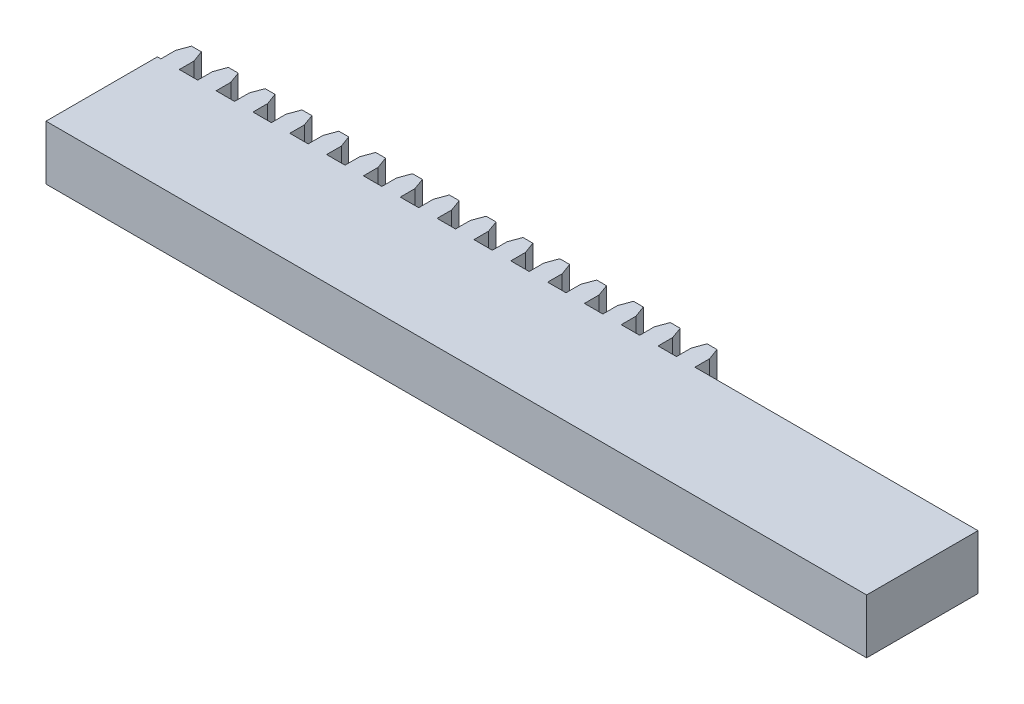
SolidWorks part; units mm, degrees
ref_plane "Front Plane" through (0, 0, 0) normal (0, 0, 1) x (1, 0, 0)
ref_plane "Top Plane" through (0, 0, 0) normal (0, 1, 0) x (1, 0, 0)
ref_plane "Right Plane" through (0, 0, 0) normal (1, 0, 0) x (0, 0, -1)
sketch "Sketch2" plane through (0, 0, 0) normal (0, 1, 0) x (1, 0, 0)
  line L0 (-1000, 0) -> (49000, 0) construction
  line L3 (0, -1000) -> (0, 49000) construction
  line L6 (-0.8429, 4.5) -> (0.8429, 4.5)
  line L7 (1.5708, 2.5) -> (1.5708, 0)
  line L8 (-1.5712, 2.5001) -> (-1.5712, 0)
  line L55 (0.8429, 4.5) -> (1.5708, 2.5)
  line L58 (-0.8429, 4.5) -> (-1.5712, 2.5001)
  line L509 (-65, 0) -> (65, 0)
  line L510 (-65, 0) -> (-65, -19)
  line L511 (-65, -19) -> (65, -19)
  line L512 (65, 0) -> (65, -19)
  point P1 (0, -19)
  point P8 (0, 4.5)
  dimension "D3" = 2
  dimension "D4" = 20
  dimension "D7" = 130
  dimension "D9" = 19
  dimension "D1" = 3.142
  dimension "D2" = 2.5
  dimension "D5" = 4.5
extrude "Boss-Extrude1" add sketch "Sketch2" along normal blind 9.3 contours L512 L509 L510 L511 region at (0, 0, 9.5)
extrude "Boss-Extrude2" add sketch "Sketch2<5>" along normal up to surface (9.3 mm away) contours L8 L509 L7 L55 L6 L58 region at (-0.0002, 0, -2.0682) up to face at (0, 9.3, 9.5)
sketch "Sketch2<5>" plane through (0, 0, 0) normal (0, 1, 0) x (1, 0, 0) same geometry as "Sketch2"
pattern_linear "LPattern1" count 11 spacing 6.2832 along (-1, 0, 0) count 5 spacing 6.2832 along (1, 0, 0) of "Boss-Extrude2"
sketch "Sketch3" plane through (65, 0, 0) normal (1, 0, 0) x (0, 0, -1)
  line L4 (-19, 0) -> (0, 0)
  line L5 (0, 0) -> (0, 9.3)
  line L6 (0, 9.3) -> (-19, 9.3)
  line L7 (-19, 9.3) -> (-19, 0)
  line L8 (-19, 0) -> (0, 0)
  line L9 (0, 0) -> (0, 9.3)
  line L10 (0, 9.3) -> (-19, 9.3)
  line L11 (-19, 9.3) -> (-19, 0)
  dimension "D1" = 0
extrude "Boss-Extrude3" add sketch "Sketch3" along normal blind 10
